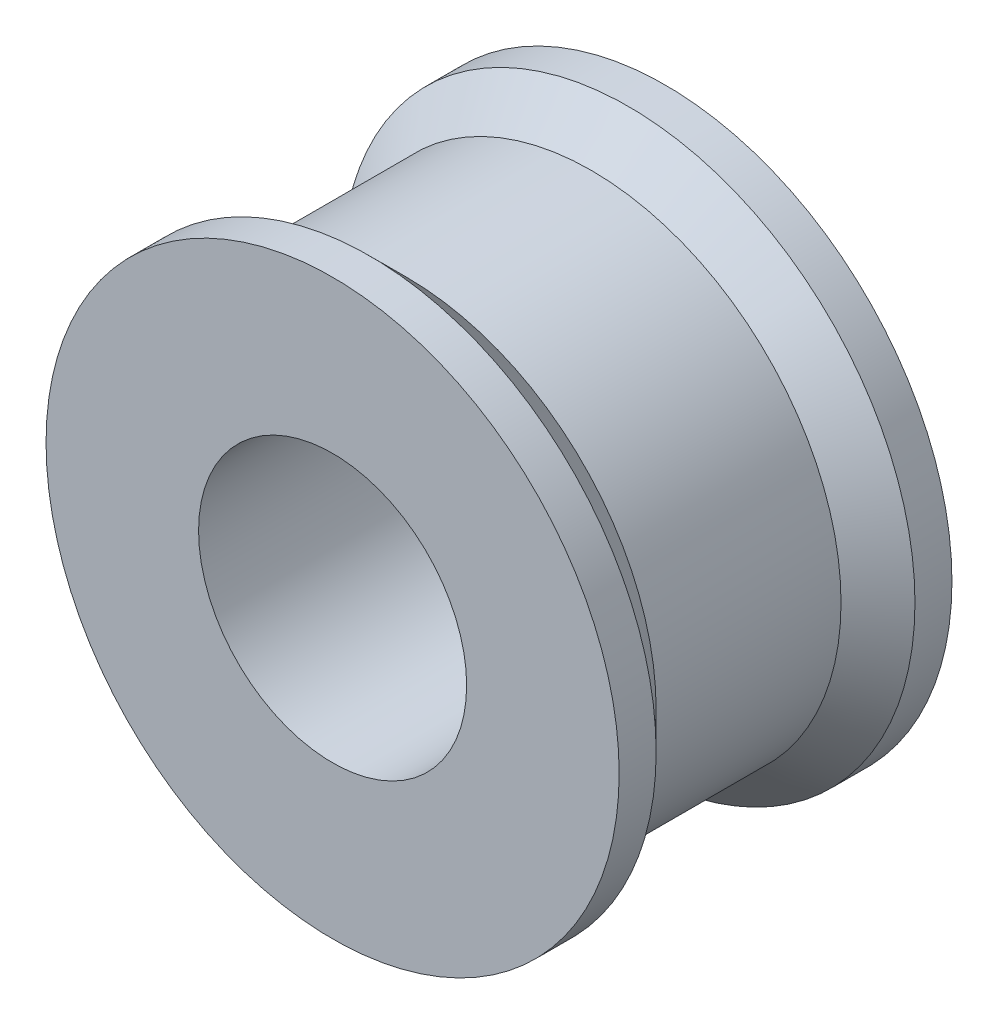
SolidWorks part; units mm, degrees
ref_plane "Front Plane" through (0, 0, 0) normal (0, 0, 1) x (1, 0, 0)
ref_plane "Top Plane" through (0, 0, 0) normal (0, 1, 0) x (1, 0, 0)
ref_plane "Right Plane" through (0, 0, 0) normal (1, 0, 0) x (0, 0, -1)
sketch "Sketch1" plane through (0, 0, 0) normal (0, 0, 1) x (1, 0, 0)
  circle A0 centre (0, 0) radius 3.625
  circle A1 centre (0, 0) radius 7.75
  dimension "D1" = 7.25
  dimension "D2" = 15.5
extrude "Boss-Extrude1" add sketch "Sketch1" along normal blind 1
sketch "Sketch2" plane through (0, 0, 1) normal (0, 0, 1) x (1, 0, 0)
  circle A0 centre (0, 0) radius 3.625
  circle A1 centre (0, 0) radius 6.75
  circle A2 centre (0, 0) radius 3.625 construction
  dimension "D1" = 13.5
extrude "Boss-Extrude2" add sketch "Sketch2" along normal blind 3.5
chamfer "Chamfer1" distance 1 angle 45 1 edges at (6.75, 0, 1)
mirror "Mirror5" about plane through (0, 0, 4.5) normal (0, 0, 1) of bodies 102
